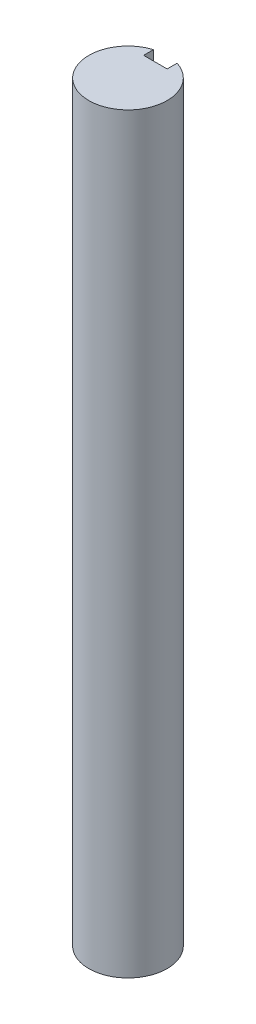
SolidWorks part; units mm, degrees
material "AISI 316 Annealed Stainless Steel Bar (SS)"
ref_plane "Front Plane" through (0, 0, 0) normal (0, 0, 1) x (1, 0, 0)
ref_plane "Top Plane" through (0, 0, 0) normal (0, 1, 0) x (1, 0, 0)
ref_plane "Right Plane" through (0, 0, 0) normal (1, 0, 0) x (0, 0, -1)
sketch "Sketch1" plane through (0, 0, 0) normal (0, 1, 0) x (1, 0, 0)
  line L0 (0, 0) -> (0, 50000) construction
  line L1 (0.3667, 0) -> (50000.3667, 0) construction
  line L2 (-1.1938, 3.7849) -> (-1.1938, 2.7781)
  line L3 (-1.1938, 2.7781) -> (0, 2.7781)
  line L4 (0, 3.9688) -> (50000, 3.9688) construction
  line L5 (1.1938, 2.7781) -> (0, 2.7781)
  line L6 (1.1938, 3.7849) -> (1.1938, 2.7781)
  arc A0 (-1.1938, 3.7849) -> (1.1938, 3.7849) centre (0, 0) ccw
  dimension "D1" = 7.9375
  dimension "D2" = 2.3876
  dimension "D3" = 1.1906
extrude "Boss-Extrude1" add sketch "Sketch1" along normal mid plane 76.2
ref_plane "keyPlane" through (0, 0, 0) normal (-1, 0, 0) x (0, 0, 1)
